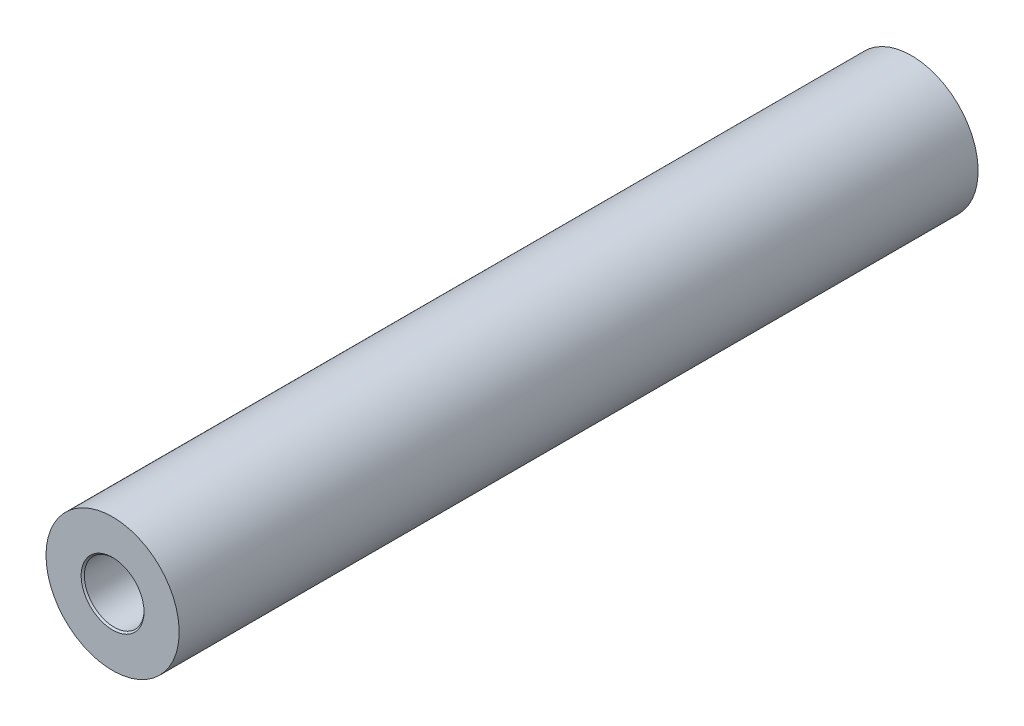
SolidWorks part; units mm, degrees
material "6061 Alloy"
ref_plane "Front Plane" through (0, 0, 0) normal (0, 0, 1) x (1, 0, 0)
ref_plane "Top Plane" through (0, 0, 0) normal (0, 1, 0) x (1, 0, 0)
ref_plane "Right Plane" through (0, 0, 0) normal (1, 0, 0) x (0, 0, -1)
sketch "Sketch3" plane through (0, 0, 0) normal (1, 0, 0) x (0, 0, -1)
  line L0 (-19.05, 0) -> (19.05, 0) construction
  line L1 (0, 3.175) -> (0, -3.175) construction
  line L2 (-19.05, 1.4224) -> (-19.05, -1.4224) construction
  point P2 (12.7, 0)
  point P3 (-12.7, 0)
  dimension "Length" = 38.1
  dimension "Min Thread Length" = 6.35
  dimension "D1" = 6.35
  dimension "Thread Dia" = 2.8448
  dimension "OD" = 6.35
ref_axis "Axis1" through (0, 3.175, 0) along (0, -1, 0)
sketch "Sketch10" plane through (0, 0, 0) normal (1, 0, 0) x (0, 0, -1)
  line L0 (19.05, 1.4224) -> (12.7, 1.4224)
  line L1 (-19.05, 1.4224) -> (-12.7, 1.4224)
  line L2 (12.7, 1.4224) -> (12.7, -1.4224)
  line L3 (-19.05, -1.4224) -> (-12.7, -1.4224)
  line L4 (-12.7, 1.4224) -> (-12.7, -1.4224)
  line L5 (12.7, -1.4224) -> (19.05, -1.4224)
sketch "Sketch13" plane through (0, 0, 0) normal (0, 0, 1) x (1, 0, 0)
  circle A0 centre (0, 0) radius 1.4224
extrude "Boss-Extrude1" add sketch "Sketch13" against normal up to vertex (-12.7 mm away) from vertex up to point (0, 0, 12.7) starting at point (0, 0, 19.05)
sketch "Sketch14" plane through (0, 0, 19.05) normal (0, 0, 1) x (1, 0, 0)
  circle A1 centre (0, 0) radius 1.4224
  circle A2 centre (0, 0) radius 1.4224
  dimension "D1" = 0
curve "Helix/Spiral2" pitch 0.635 height 6.985 turns 11 parameters "Pitch"=0.635
sketch "Sketch16" plane through (0, 0, 19.05) normal (0, 0, 1) x (1, 0, 0)
  circle A2 centre (0, 0) radius 1.4986
  circle A3 centre (0, 0) radius 1.4986
  dimension "D1" = 0.0762
extrude "Boss-Extrude2" add sketch "Sketch16" against normal through all draft 45
pattern_circular "CirPattern1" count 2 over 180 about axis through (0, 3.175, 0) along (0, -1, 0) of bodies 113
sketch "Sketch1" plane through (0, 0, 0) normal (0, 0, 1) x (1, 0, 0)
  circle A1 centre (0, 0) radius 1.4224 construction
  circle A2 centre (0, 0) radius 3.175
extrude "Extrude1" add sketch "Sketch1" along normal up to vertex (19.05 mm away) and the other way up to vertex (19.05 mm away) up to point (0, 0, 19.05) other way up to point (0, 0, -19.05)
combine bodies "Combine1" operation type subtract main body 101 bodies to subtract 114 113
equation "\"D1@Sketch3\" = \"Min Thread Length@Sketch3\""
equation "\"D3@Helix/Spiral2\" = \"Min Thread Length@Sketch3\"+\"Pitch@Helix/Spiral2\""
